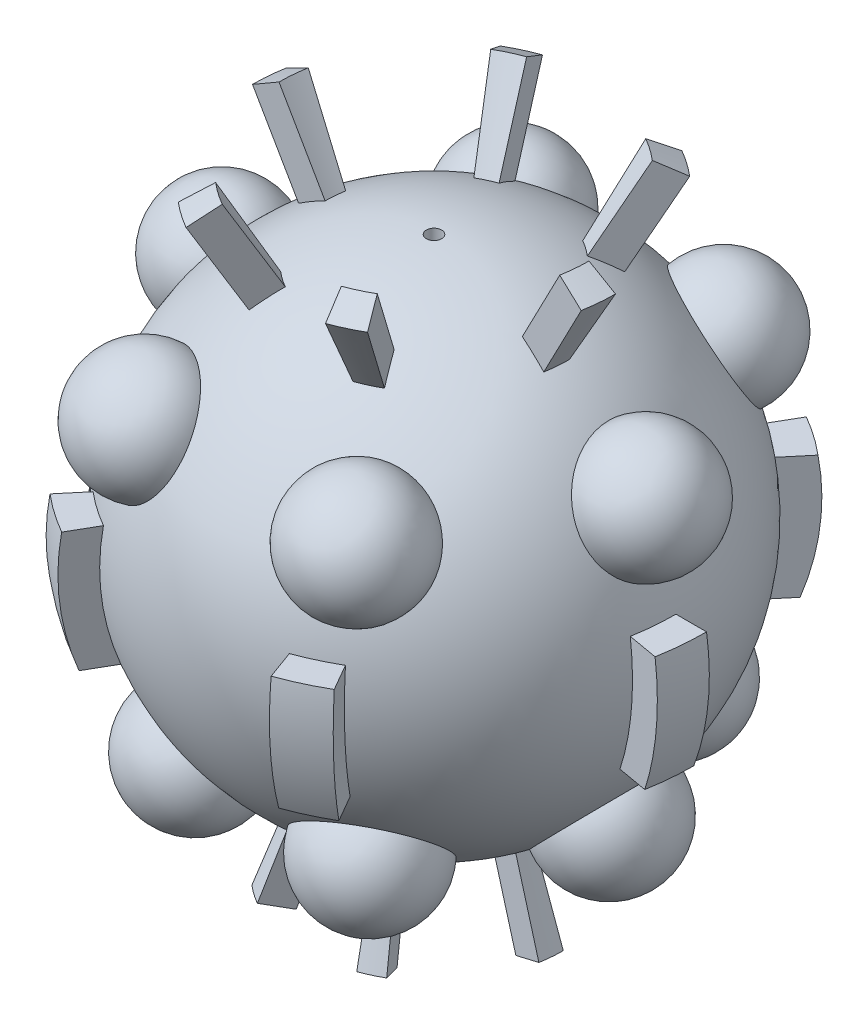
SolidWorks part; units mm, degrees
ref_plane "Front Plane" through (0, 0, 0) normal (0, 0, 1) x (1, 0, 0)
ref_plane "Top Plane" through (0, 0, 0) normal (0, 1, 0) x (1, 0, 0)
ref_plane "Right Plane" through (0, 0, 0) normal (1, 0, 0) x (0, 0, -1)
sketch "Sketch1" plane through (0, 0, 0) normal (0, 0, 1) x (1, 0, 0)
  line L0 (0, 203.2) -> (0, -203.2)
  line L1 (0, 0) -> (-101.6, 175.9764) construction
  line L2 (-101.6, 175.9764) -> (-139.7, 241.9675) construction
  line L3 (-90.4028, 181.9823) -> (-128.7015, 248.3175)
  line L4 (-112.3999, 169.2823) -> (-150.6985, 235.6175)
  line L5 (-150.6985, 235.6175) -> (-128.7015, 248.3175)
  line L6 (-112.5985, 169.6264) -> (-150.6985, 235.6175) construction
  line L7 (-90.6015, 182.3264) -> (-128.7015, 248.3175) construction
  line L8 (0, 0) -> (-175.9764, 101.6) construction
  line L9 (-175.9764, 101.6) -> (-219.9705, 127)
  line L10 (-200.9066, 30.4433) -> (-226.3066, 30.4433)
  line L11 (-0.9431, -20.3567) -> (-202.1778, -20.3567) construction
  line L12 (-190.3338, -71.1567) -> (-215.7338, -71.1567)
  line L13 (-81.1528, -186.2914) -> (-107.3506, -258.2692)
  line L14 (-83.777, -266.8493) -> (-107.3506, -258.2692)
  line L15 (-57.5792, -194.8714) -> (-83.777, -266.8493)
  line L16 (0, 0) -> (-95.5638, -262.5593) construction
  line L18 (0, 0) -> (-145.2763, 142.074) construction
  line L19 (0, 0) -> (-175.9764, -101.6) construction
  line L20 (0, 0) -> (-145.2763, -142.074) construction
  line L21 (-145.2763, -142.074) -> (-181.5954, -177.5925)
  arc A0 (0, 203.2) -> (0, -203.2) centre (0, 0) ccw
  arc A1 (-145.2763, 142.074) -> (-195.6779, 54.776) centre (-175.9764, 101.6) ccw
  arc A2 (-175.9764, -101.6) -> (-105.4965, -173.6684) centre (-145.2763, -142.074) ccw
  arc A3 (-215.7338, -71.1567) -> (-226.3066, 30.4433) centre (-25.4, 0) cw
  point P13 (0, 0)
  point P27 (0, 0)
  point P29 (0, 0)
  point P30 (-59.1376, -194.4042)
  dimension "D1" = 203.2
  dimension "D6" = 50.8
  dimension "D14" = 203.2
  dimension "D2" = 76.2
  dimension "D5" = 30
  dimension "D7" = 60
  dimension "D9" = 90
  dimension "D11" = 120
  dimension "D12" = 50.8
  dimension "D8" = 25.4
  dimension "D13" = 50.8
  dimension "D15" = 20
  dimension "D3" = 12.7
  dimension "D4" = 12.7
  dimension "D10" = 2
revolve "Revolve1" add sketch "Sketch1" angle 360 about L0 region at (-86.2408, 0, 0)
sketch "Sketch2" plane through (0, 0, 0) normal (0, 1, 0) x (1, 0, 0)
  circle A0 centre (0, 0) radius 6.35
  dimension "D1" = 12.7
extrude "Cut-Extrude1" cut sketch "Sketch2" against normal blind 255.524 and the other way blind 274.32
revolve "Revolve2" add sketch "Sketch1<4>" angle 10 about L0 region at (-120.6169, 208.9145, 0) region at (-82.509, -226.6917, 0) region at (-212.7069, -20.3567, 0)
sketch "Sketch1<4>" plane through (0, 0, 0) normal (0, 0, 1) x (1, 0, 0) same geometry as "Sketch1"
revolve "Revolve4" add sketch "Sketch1<6>" angle 360 about L8 region at (-182.4268, 131.1798, 0)
sketch "Sketch1<6>" plane through (0, 0, 0) normal (0, 0, 1) x (1, 0, 0) same geometry as "Sketch1"
revolve "Revolve10" add sketch "Sketch1<11>" angle 360 about L20 region at (-175.5, -140.3119, 0)
sketch "Sketch1<11>" plane through (0, 0, 0) normal (0, 0, 1) x (1, 0, 0) same geometry as "Sketch1"
pattern_circular "CirPattern1" count 6 over 360 of "Revolve4", "Revolve2", "Revolve10"
